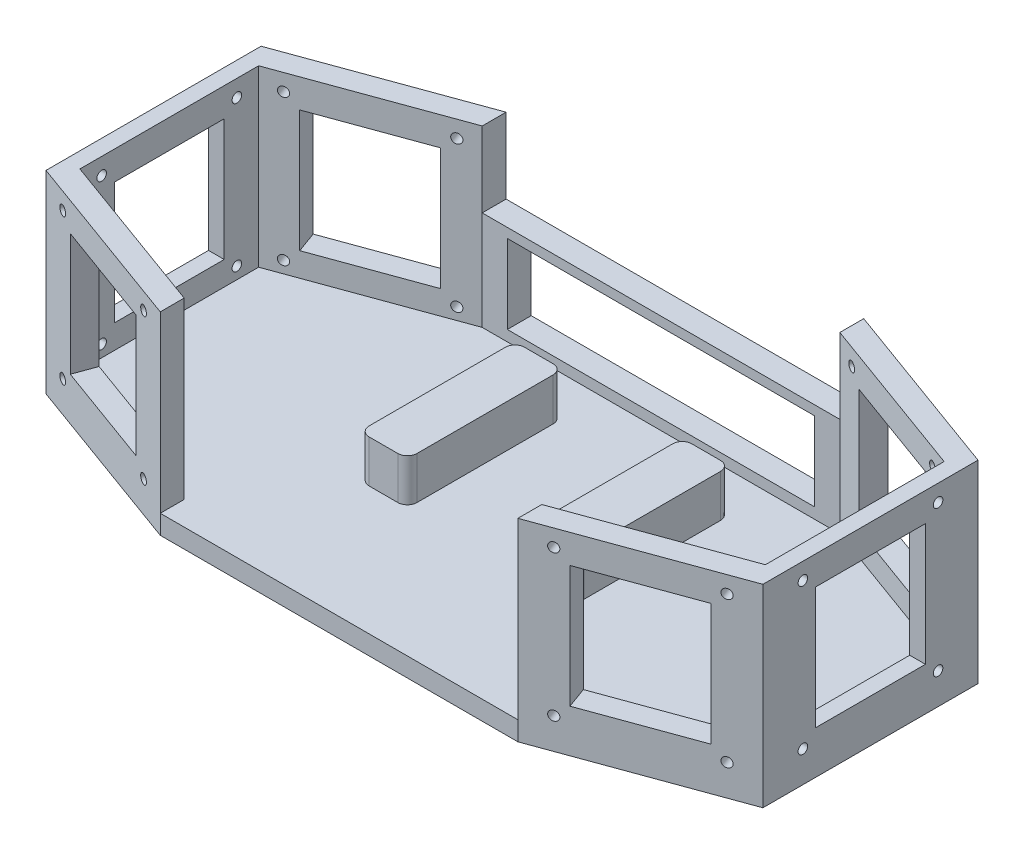
SolidWorks part; units mm, degrees
material "ABS"
ref_plane "Front Plane" through (0, 0, 0) normal (0, 0, 1) x (1, 0, 0)
ref_plane "Top Plane" through (0, 0, 0) normal (0, 1, 0) x (1, 0, 0)
ref_plane "Right Plane" through (0, 0, 0) normal (1, 0, 0) x (0, 0, -1)
sketch "Sketch1" plane through (0, 0, 0) normal (0, 1, 0) x (1, 0, 0)
  line L0 (-150, 0) -> (150, 0) construction
  line L1 (-150, 45) -> (-150, -45)
  line L2 (140.0883, -41.1583) -> (79.948, -63.0476) construction
  line L3 (-140.0883, 41.1583) -> (-142.4825, 47.7362) construction
  line L4 (-140.0883, 41.1583) -> (-79.948, 63.0476) construction
  line L5 (-150, 45) -> (-74.8246, 72.3616)
  line L6 (-79.948, 63.0476) -> (-82.3421, 69.6255) construction
  line L7 (-143, 32) -> (-143, -32) construction
  line L8 (-140.0883, -41.1583) -> (-142.4825, -47.7362) construction
  line L9 (-79.948, -63.0476) -> (-82.3421, -69.6255) construction
  line L10 (-140.0883, -41.1583) -> (-79.948, -63.0476) construction
  line L11 (-150, -45) -> (-74.8246, -72.3616)
  line L12 (0, 74.8501) -> (0, -82.9126) construction
  line L13 (79.948, -63.0476) -> (82.3421, -69.6255) construction
  line L14 (140.0883, -41.1583) -> (142.4825, -47.7362) construction
  line L15 (143, 32) -> (143, -32) construction
  line L16 (79.948, 63.0476) -> (82.3421, 69.6255) construction
  line L17 (140.0883, 41.1583) -> (79.948, 63.0476) construction
  line L18 (140.0883, 41.1583) -> (142.4825, 47.7362) construction
  line L19 (150, -45) -> (74.8246, -72.3616)
  line L20 (150, 45) -> (74.8246, 72.3616)
  line L21 (150, 45) -> (150, -45)
  line L22 (-74.8246, 72.3616) -> (74.8246, 72.3616)
  line L23 (-74.8246, -72.3616) -> (74.8246, -72.3616)
  point P0 (0, 0)
  point P3 (-150, 0)
  point P10 (-143, 0)
  point P13 (0, 0)
  point P37 (143, 0)
  dimension "D1" = 7
  dimension "D2" = 90
  dimension "D3" = 64
  dimension "D4" = 300
  dimension "D5" = 7
  dimension "D6" = 8
  dimension "D7" = 80
  dimension "D8" = 110
extrude "Boss-Extrude1" add sketch "Sketch1" along normal blind 8
sketch "Sketch2" plane through (0, 8, 0) normal (0, 1, 0) x (1, 0, 0)
  line L0 (0, 72.3616) -> (0, -72.3616) construction
  line L1 (74.8246, 72.3616) -> (-74.8246, 72.3616) construction
  line L2 (-74.8246, -72.3616) -> (74.8246, -72.3616) construction
  line L3 (-74.8246, -72.3616) -> (-74.8246, -62.3616) construction
  line L4 (-74.8246, -62.3616) -> (-64.3246, -62.3616) construction
  line L5 (-64.3246, -62.3616) -> (-64.3246, -72.3616) construction
  line L6 (-64.3246, -72.3616) -> (-74.8246, -72.3616) construction
  line L7 (64.3246, -72.3616) -> (74.8246, -72.3616) construction
  line L8 (64.3246, -62.3616) -> (64.3246, -72.3616) construction
  line L9 (74.8246, -62.3616) -> (64.3246, -62.3616) construction
  line L10 (74.8246, -72.3616) -> (74.8246, -62.3616) construction
  line L11 (-150, 0) -> (150, 0) construction
  line L12 (-150, 45) -> (-150, -45) construction
  line L13 (150, -45) -> (150, 45) construction
  line L14 (74.8246, 72.3616) -> (74.8246, 62.3616)
  line L15 (74.8246, 62.3616) -> (64.3246, 62.3616)
  line L16 (64.3246, 62.3616) -> (64.3246, 72.3616)
  line L17 (64.3246, 72.3616) -> (74.8246, 72.3616)
  line L18 (-64.3246, 72.3616) -> (-74.8246, 72.3616)
  line L19 (-64.3246, 62.3616) -> (-64.3246, 72.3616)
  line L20 (-74.8246, 62.3616) -> (-64.3246, 62.3616)
  line L21 (-74.8246, 72.3616) -> (-74.8246, 62.3616)
  dimension "D1" = 10.5
  dimension "D2" = 10
extrude "Boss-Extrude2" add sketch "Sketch2" along normal blind 37.5
sketch "Sketch4" plane through (0, 8, 0) normal (0, 1, 0) x (1, 0, 0)
  line L1 (-64.3246, 72.3616) -> (64.3246, 72.3616)
  line L2 (-64.3246, 72.3616) -> (-64.3246, 62.3616)
  line L3 (-64.3246, 62.3616) -> (64.3246, 62.3616)
  line L4 (64.3246, 72.3616) -> (64.3246, 62.3616)
extrude "Boss-Extrude4" add sketch "Sketch4" along normal blind 4.5
sketch "Sketch5" plane through (0, 8, 0) normal (0, 1, 0) x (1, 0, 0)
  line L0 (-74.8246, 62.3616) -> (-87.0406, 57.9153)
  line L1 (-74.8246, 72.3616) -> (-150, 45) construction
  line L2 (-74.8246, 72.3616) -> (-74.8246, 62.3616)
  line L3 (-74.8246, 72.3616) -> (-150, 45)
  line L4 (-87.0406, 57.9153) -> (-140.6031, 38.4202)
  line L5 (-150, 45) -> (-140.6031, 38.4202) construction
  line L6 (-74.8246, -72.3616) -> (-74.8246, -62.3616)
  line L7 (-140.6031, 38.4202) -> (-143.4222, 37.3941)
  line L8 (-150, 45) -> (-143.4222, 37.3941) construction
  line L9 (-150, 0) -> (-74.8246, 0) construction
  line L10 (-150, 45) -> (-150, -45) construction
  line L11 (-79.6003, 0) -> (86.9407, 0) construction
  line L12 (-124.0599, 0) -> (-121.8599, 0) construction
  line L13 (-74.8246, -62.3616) -> (-87.0406, -57.9153)
  line L14 (-140.6031, -38.4202) -> (-143.4222, -37.3941)
  line L15 (-87.0406, -57.9153) -> (-140.6031, -38.4202)
  line L16 (-150, -45) -> (-143.4222, -37.3941) construction
  line L17 (-74.8246, -72.3616) -> (-150, -45)
  line L18 (-143.4222, 37.3941) -> (-143.4222, -37.3941)
  line L19 (-150, 45) -> (-150, -45)
  line L20 (0, 72.1209) -> (0, -72.3616) construction
  line L21 (-74.8246, -72.3616) -> (74.8246, -72.3616) construction
  line L22 (150, -45) -> (143.4222, -37.3941) construction
  line L23 (150, 0) -> (74.8246, 0) construction
  line L24 (150, 45) -> (143.4222, 37.3941) construction
  line L25 (150, 45) -> (140.6031, 38.4202) construction
  line L26 (150, 45) -> (150, -45)
  line L27 (143.4222, 37.3941) -> (143.4222, -37.3941)
  line L28 (74.8246, -72.3616) -> (150, -45)
  line L29 (87.0406, -57.9153) -> (140.6031, -38.4202)
  line L30 (140.6031, -38.4202) -> (143.4222, -37.3941)
  line L31 (74.8246, -62.3616) -> (87.0406, -57.9153)
  line L32 (140.6031, 38.4202) -> (143.4222, 37.3941)
  line L33 (74.8246, -72.3616) -> (74.8246, -62.3616)
  line L34 (87.0406, 57.9153) -> (140.6031, 38.4202)
  line L35 (74.8246, 72.3616) -> (150, 45)
  line L36 (74.8246, 72.3616) -> (74.8246, 62.3616)
  line L37 (74.8246, 62.3616) -> (87.0406, 57.9153)
  dimension "D1" = 13
  dimension "D2" = 55
  dimension "D3" = 3
extrude "Boss-Extrude5" add sketch "Sketch5" along normal blind 10
sketch "Sketch6" plane through (0, 45.5, 0) normal (0, 1, 0) x (1, 0, 0)
  line L1 (74.8246, 72.3616) -> (-74.8246, 72.3616)
  line L2 (74.8246, 72.3616) -> (74.8246, 62.3616)
  line L3 (74.8246, 62.3616) -> (-74.8246, 62.3616)
  line L4 (-74.8246, 72.3616) -> (-74.8246, 62.3616)
extrude "Boss-Extrude6" add sketch "Sketch6" along normal blind 4
sketch "Sketch7" plane through (32.0094, 0, -87.9451) normal (0.342, 0, -0.9397) x (-0.9397, 0, -0.342)
  line L0 (-85.563, 18) -> (-85.563, 0) construction
  line L1 (-125.563, 18) -> (-45.563, 18) construction
  line L2 (-125.563, 0) -> (-45.563, 0) construction
  line L3 (-113.853, 13) -> (-85.563, 13) construction
  circle A0 centre (-113.853, 13) radius 2
  circle A1 centre (-57.273, 13) radius 2
  dimension "D1" = 56.58
  dimension "D2" = 4
  dimension "D3" = 5
extrude "Cut-Extrude1" cut sketch "Sketch7" against normal up to next
ref_plane "Plane1" through (0, 0, 0) normal (1, 0, 0) x (0, 0, -1)
mirror "Mirror1" about plane through (0, 0, 0) normal (1, 0, 0) of "Cut-Extrude1"
ref_plane "Plane2" through (0, 0, 0) normal (0, 0, -1) x (-1, 0, 0)
mirror "Mirror2" about plane through (0, 0, 0) normal (0, 0, -1) of "Cut-Extrude1", "Mirror1"
sketch "Sketch8" plane through (150, 0, 0) normal (1, 0, 0) x (0, 0, -1)
  line L0 (0, 18) -> (0, 0) construction
  line L1 (-45, 18) -> (45, 18) construction
  line L2 (-28.29, 13) -> (28.29, 13) construction
  line L3 (0, -27.225) -> (0, 27.225) construction
  circle A0 centre (-28.29, 13) radius 2
  circle A1 centre (28.29, 13) radius 2
  point P8 (0, 13)
  dimension "D1" = 56.58
  dimension "D3" = 4
  dimension "D2" = 5
extrude "Cut-Extrude2" cut sketch "Sketch8" against normal up to next
mirror "Mirror3" about plane through (0, 0, 0) normal (1, 0, 0) of "Cut-Extrude2"
sketch "Sketch9" plane through (0, 18, 0) normal (0, 1, 0) x (1, 0, 0)
  line L0 (143.4222, 23) -> (150, 23)
  line L1 (143.4222, 37.3941) -> (143.4222, -37.3941) construction
  line L2 (150, -45) -> (150, 45) construction
  line L3 (150, 23) -> (150, 45)
  line L4 (150, 45) -> (134.0252, 50.8143)
  line L5 (150, 45) -> (74.8246, 72.3616) construction
  line L6 (134.0252, 50.8143) -> (130.8113, 41.9841)
  line L7 (74.8246, 62.3616) -> (143.4222, 37.3941) construction
  line L8 (130.8113, 41.9841) -> (143.4222, 37.3941)
  line L9 (143.4222, 37.3941) -> (143.4222, 23)
  line L12 (74.8246, 72.3616) -> (90.7994, 66.5473)
  line L13 (90.7994, 66.5473) -> (87.5854, 57.717)
  line L14 (87.5854, 57.717) -> (74.8246, 62.3616)
  line L15 (74.8246, 72.3616) -> (74.8246, 62.3616) construction
  line L16 (74.8246, 62.3616) -> (74.8246, 72.3616)
  line L17 (0, -70.7131) -> (0, 92.4677) construction
  line L18 (-74.8246, 62.3616) -> (-74.8246, 72.3616)
  line L19 (-87.5854, 57.717) -> (-74.8246, 62.3616)
  line L20 (-90.7994, 66.5473) -> (-87.5854, 57.717)
  line L21 (-74.8246, 72.3616) -> (-90.7994, 66.5473)
  line L22 (-143.4222, 37.3941) -> (-143.4222, 23)
  line L23 (-130.8113, 41.9841) -> (-143.4222, 37.3941)
  line L24 (-134.0252, 50.8143) -> (-130.8113, 41.9841)
  line L25 (-150, 45) -> (-134.0252, 50.8143)
  line L26 (-150, 23) -> (-150, 45)
  line L27 (-143.4222, 23) -> (-150, 23)
  line L28 (150, 0) -> (-150, 0) construction
  line L29 (-150, 45) -> (-150, -45) construction
  line L30 (143.4222, -37.3941) -> (143.4222, -23)
  line L31 (130.8113, -41.9841) -> (143.4222, -37.3941)
  line L32 (134.0252, -50.8143) -> (130.8113, -41.9841)
  line L33 (150, -45) -> (134.0252, -50.8143)
  line L34 (150, -23) -> (150, -45)
  line L35 (143.4222, -23) -> (150, -23)
  line L36 (-143.4222, -23) -> (-150, -23)
  line L37 (-150, -23) -> (-150, -45)
  line L38 (-150, -45) -> (-134.0252, -50.8143)
  line L39 (-134.0252, -50.8143) -> (-130.8113, -41.9841)
  line L40 (-130.8113, -41.9841) -> (-143.4222, -37.3941)
  line L41 (-143.4222, -37.3941) -> (-143.4222, -23)
  line L42 (-74.8246, -72.3616) -> (-90.7994, -66.5473)
  line L43 (-90.7994, -66.5473) -> (-87.5854, -57.717)
  line L44 (-87.5854, -57.717) -> (-74.8246, -62.3616)
  line L45 (-74.8246, -62.3616) -> (-74.8246, -72.3616)
  line L46 (74.8246, -62.3616) -> (74.8246, -72.3616)
  line L47 (87.5854, -57.717) -> (74.8246, -62.3616)
  line L48 (90.7994, -66.5473) -> (87.5854, -57.717)
  line L49 (74.8246, -72.3616) -> (90.7994, -66.5473)
  dimension "D1" = 22
  dimension "D2" = 17
  dimension "D3" = 17
extrude "Boss-Extrude8" add sketch "Sketch9" along normal blind 63
sketch "Sketch10" plane through (32.0094, 0, -87.9451) normal (0.342, 0, -0.9397) x (-0.9397, 0, -0.342)
  line L0 (-85.563, 0) -> (-85.563, 86.9159) construction
  line L1 (-125.563, 0) -> (-45.563, 0) construction
  line L2 (-113.853, 13) -> (-113.853, 74) construction
  circle A0 centre (-113.853, 74) radius 2
  circle A1 centre (-113.853, 13) radius 2 construction
  circle A2 centre (-57.273, 74) radius 2
  dimension "D1" = 61
extrude "Cut-Extrude3" cut sketch "Sketch10" against normal up to next
mirror "Mirror4" about plane through (0, 0, 0) normal (1, 0, 0) of "Cut-Extrude3"
mirror "Mirror5" about plane through (0, 0, 0) normal (0, 0, -1) of "Cut-Extrude3", "Mirror4"
sketch "Sketch11" plane through (150, 0, 0) normal (1, 0, 0) x (0, 0, -1)
  line L0 (-28.29, 13) -> (-28.29, 74) construction
  line L1 (0, 18) -> (0, 79.1024) construction
  line L2 (-23, 18) -> (23, 18) construction
  circle A0 centre (-28.29, 74) radius 2
  circle A1 centre (-28.29, 13) radius 2 construction
  circle A2 centre (28.29, 74) radius 2
  dimension "D1" = 61
extrude "Cut-Extrude4" cut sketch "Sketch11" against normal up to next
mirror "Mirror6" about plane through (0, 0, 0) normal (1, 0, 0) of "Cut-Extrude4"
sketch "Sketch12" plane through (0, 81, 0) normal (0, 1, 0) x (1, 0, 0)
  line L0 (130.8113, 41.9841) -> (87.5854, 57.717)
  line L1 (87.5854, 57.717) -> (90.7994, 66.5473)
  line L2 (90.7994, 66.5473) -> (134.0252, 50.8143)
  line L3 (134.0252, 50.8143) -> (130.8113, 41.9841)
  line L4 (0, 103.9036) -> (0, -116.4859) construction
  line L5 (143.4222, 23) -> (150, 23)
  line L6 (143.4222, 23) -> (143.4222, -23)
  line L7 (143.4222, -23) -> (150, -23)
  line L8 (150, 23) -> (150, -23)
  line L9 (150, 0) -> (-150, 0) construction
  line L10 (-150, 23) -> (-150, -23) construction
  line L11 (134.0252, -50.8143) -> (130.8113, -41.9841)
  line L12 (90.7994, -66.5473) -> (134.0252, -50.8143)
  line L13 (87.5854, -57.717) -> (90.7994, -66.5473)
  line L14 (130.8113, -41.9841) -> (87.5854, -57.717)
  line L15 (-130.8113, -41.9841) -> (-87.5854, -57.717)
  line L16 (-87.5854, -57.717) -> (-90.7994, -66.5473)
  line L17 (-90.7994, -66.5473) -> (-134.0252, -50.8143)
  line L18 (-134.0252, -50.8143) -> (-130.8113, -41.9841)
  line L19 (-150, 23) -> (-150, -23)
  line L20 (-143.4222, -23) -> (-150, -23)
  line L21 (-143.4222, 23) -> (-143.4222, -23)
  line L22 (-143.4222, 23) -> (-150, 23)
  line L23 (-134.0252, 50.8143) -> (-130.8113, 41.9841)
  line L24 (-90.7994, 66.5473) -> (-134.0252, 50.8143)
  line L25 (-87.5854, 57.717) -> (-90.7994, 66.5473)
  line L26 (-130.8113, 41.9841) -> (-87.5854, 57.717)
extrude "Boss-Extrude9" add sketch "Sketch12" against normal blind 12
sketch "Sketch13" plane through (0, 8, 0) normal (0, 1, 0) x (1, 0, 0)
  line L0 (0, 62.3616) -> (0, -72.3616) construction
  line L1 (-41, 46.2316) -> (-29, 46.2316)
  line L2 (-45, 42.2316) -> (-45, -14.7684)
  line L3 (-41, -18.7684) -> (-29, -18.7684)
  line L4 (45, 42.2316) -> (45, -14.7684)
  line L5 (-74.8246, 62.3616) -> (74.8246, 62.3616) construction
  line L6 (-74.8246, -72.3616) -> (74.8246, -72.3616) construction
  line L7 (-25, 42.2316) -> (-25, -14.7684)
  line L8 (25, 42.2316) -> (25, -14.7684)
  line L9 (29, 46.2316) -> (41, 46.2316)
  line L10 (29, -18.7684) -> (41, -18.7684)
  line L11 (-25, 46.2316) -> (25, 46.2316) construction
  line L12 (-25, -18.7684) -> (25, -18.7684) construction
  arc A0 (-45, -14.7684) -> (-41, -18.7684) centre (-41, -14.7684) ccw
  arc A1 (41, -18.7684) -> (45, -14.7684) centre (41, -14.7684) ccw
  arc A2 (41, 46.2316) -> (45, 42.2316) centre (41, 42.2316) cw
  arc A3 (-41, 46.2316) -> (-45, 42.2316) centre (-41, 42.2316) ccw
  arc A4 (25, -14.7684) -> (29, -18.7684) centre (29, -14.7684) ccw
  arc A5 (25, 42.2316) -> (29, 46.2316) centre (29, 42.2316) cw
  arc A6 (-25, 42.2316) -> (-29, 46.2316) centre (-29, 42.2316) ccw
  arc A7 (-25, -14.7684) -> (-29, -18.7684) centre (-29, -14.7684) cw
  point P10 (0, 46.2316)
  point P15 (45, -18.7684)
  point P18 (45, 46.2316)
  point P21 (-45, 46.2316)
  dimension "D4" = 4
  dimension "D7" = 4
  dimension "D1" = 65
  dimension "D2" = 90
  dimension "D3" = 16.13
  dimension "D5" = 20
  dimension "D6" = 25
extrude "Boss-Extrude10" add sketch "Sketch13" along normal blind 17.79
sketch "Sketch14" plane through (0, 25.79, 0) normal (0, 1, 0) x (1, 0, 0)
  circle A0 centre (-35, 39.7244) radius 1.5
  circle A1 centre (-35, -8.0256) radius 1.5
  dimension "D1" = 3
  dimension "D2" = 47.75
